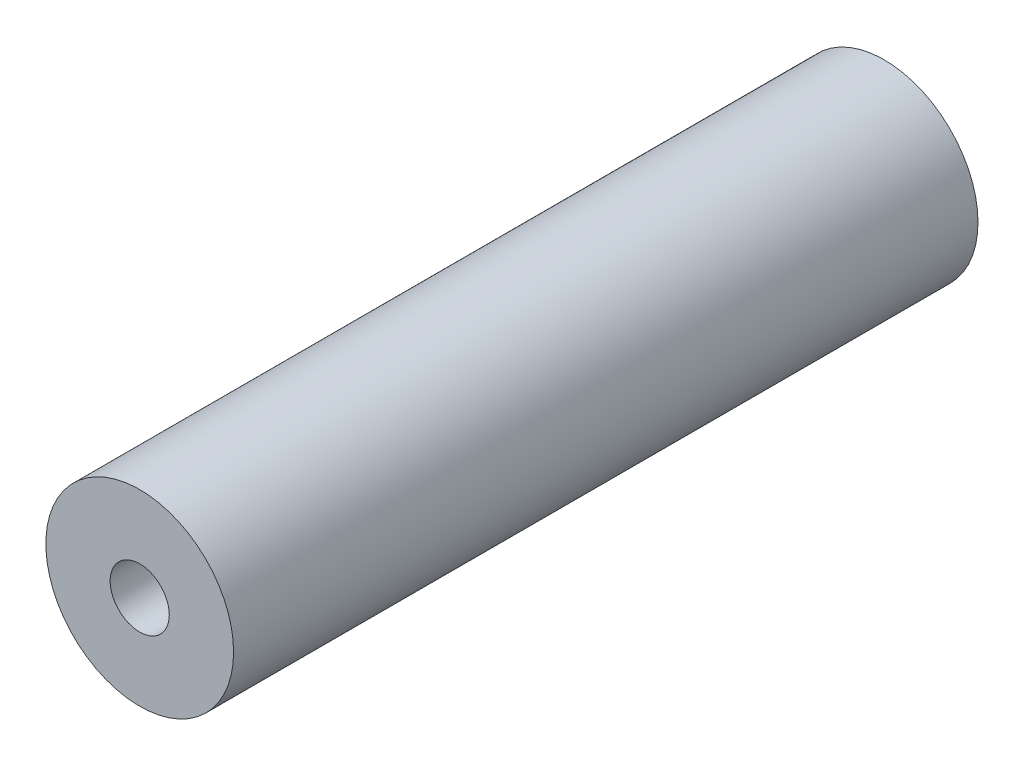
SolidWorks part; units mm, degrees
ref_plane "Front Plane" through (0, 0, 0) normal (0, 0, 1) x (1, 0, 0)
ref_plane "Top Plane" through (0, 0, 0) normal (0, 1, 0) x (1, 0, 0)
ref_plane "Right Plane" through (0, 0, 0) normal (1, 0, 0) x (0, 0, -1)
sketch "Sketch1" plane through (0, 0, 0) normal (0, 0, 1) x (1, 0, 0)
  circle A0 centre (0, 0) radius 3.9688
  dimension "D1" = 7.9375
extrude "Boss-Extrude1" add sketch "Sketch1" along normal blind 31.475
sketch "Sketch3" plane through (0, 0, 31.475) normal (0, 0, 1) x (1, 0, 0)
  circle A0 centre (0, 0) radius 1.25
  dimension "D1" = 2.5
extrude "Cut-Extrude1" cut sketch "Sketch3" against normal blind 4.5
sketch "Sketch4" plane through (0, 0, 0) normal (0, 0, -1) x (-1, 0, 0)
  circle A0 centre (0, 0) radius 1.3521
extrude "Cut-Extrude2" cut sketch "Sketch4" against normal blind 4.5
